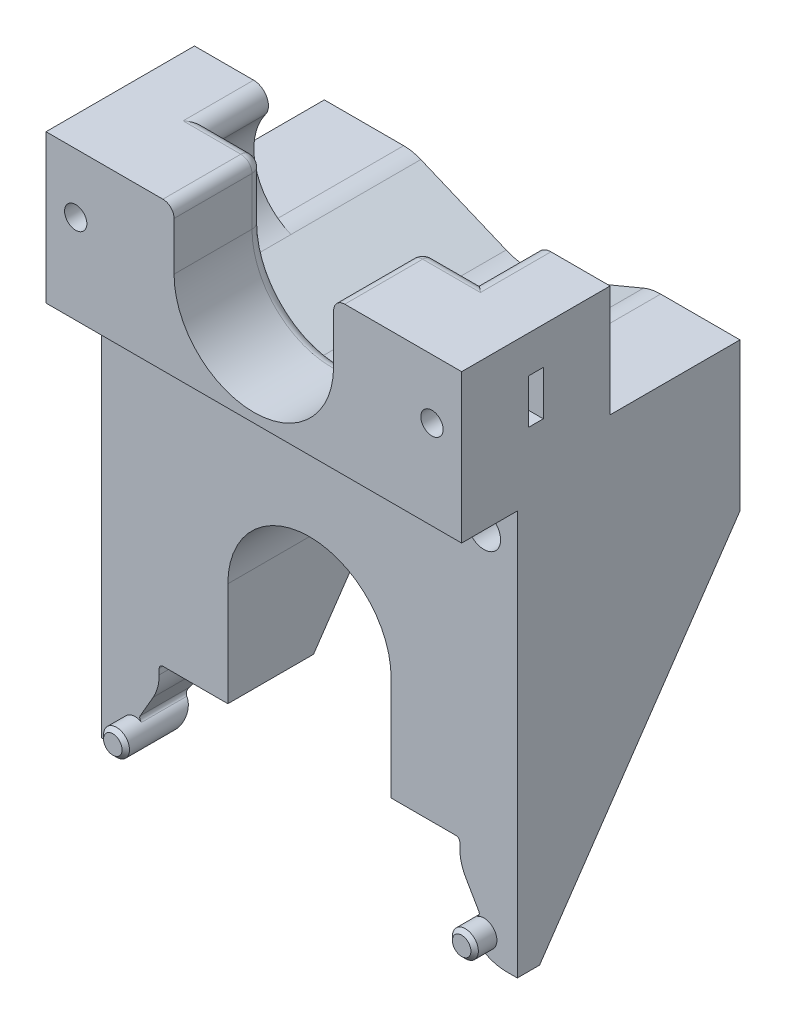
SolidWorks part; units mm, degrees
ref_plane "Front Plane" through (0, 0, 0) normal (0, 0, 1) x (1, 0, 0)
ref_plane "Top Plane" through (0, 0, 0) normal (0, 1, 0) x (1, 0, 0)
ref_plane "Right Plane" through (0, 0, 0) normal (1, 0, 0) x (0, 0, -1)
sketch "Sketch2" plane through (0, 0, 0) normal (0, 0, 1) x (1, 0, 0)
  line L0 (0, 28) -> (0, 0) construction
  line L1 (-23.5, -23.5) -> (23.5, -23.5) construction
  line L2 (-23.5, -23.5) -> (-23.5, 23.5) construction
  line L3 (-23.5, 23.5) -> (23.5, 23.5) construction
  line L4 (23.5, -23.5) -> (23.5, 23.5) construction
  line L5 (-23.5, -23.5) -> (23.5, 23.5) construction
  line L6 (-23.5, 23.5) -> (23.5, -23.5) construction
  line L7 (-28, -37) -> (28, -37) construction
  line L8 (-28, -37) -> (-28, 28) construction
  line L9 (-28, 28) -> (28, 28) construction
  line L10 (28, -37) -> (28, 28) construction
  line L11 (0, 0) -> (-28, 0) construction
  line L12 (-23.5, -25.5) -> (-23.5, -26.5) construction
  line L13 (-23.5, -26.5) -> (23.5, -26.5) construction
  line L14 (23.5, -26.5) -> (23.5, -25.5) construction
  line L15 (-23.5, -25.5) -> (23.5, -25.5) construction
  line L16 (0, 28) -> (0, 29.5) construction
  line L17 (0, 29.5) -> (0, 40) construction
  circle A0 centre (23.5, 23.5) radius 2 construction
  circle A1 centre (-23.5, 23.5) radius 2.25
  circle A2 centre (-23.5, -23.5) radius 1.75
  circle A3 centre (23.5, -23.5) radius 2 construction
  circle A4 centre (23.5, 23.5) radius 2.25
  circle A5 centre (23.5, -23.5) radius 1.75
  circle A6 centre (0, 40) radius 10.5 construction
  point P0 (0, 0)
  point P20 (0, 0)
  point P26 (0, 0)
  point P28 (0, 0)
  point P31 (0, 0)
  dimension "D3" = 4
  dimension "D8" = 21
  dimension "D1" = 47
  dimension "D5" = 56
  dimension "D6" = 65
  dimension "D7" = 1
  dimension "D9" = 1.5
  dimension "D4" = 0.25
sketch "Sketch3" plane through (0, 0, 0) normal (1, 0, 0) x (0, 0, -1)
  line L0 (0, -26.5) -> (0, 0)
  line L1 (0, 0) -> (0, 28)
  line L3 (30, 48) -> (30, 13)
  line L4 (30, 13) -> (3, -26.5)
  line L5 (3, -26.5) -> (0, -26.5)
  line L6 (30, 48) -> (-7.5, 48)
  line L7 (-7.5, 48) -> (-7.5, 28)
  line L8 (-7.5, 28) -> (0, 28)
  line L9 (0, 28) -> (30, 28) construction
  line L10 (3, -26.5) -> (22.1727, -26.5) construction
  dimension "D1" = 15
  dimension "D2" = 20
  dimension "D3" = 30
  dimension "D4" = 3
  dimension "D5" = 55.646
  dimension "D6" = 7.5
extrude "Boss-Extrude1" add sketch "Sketch3" along normal up to vertex (28 mm away) and the other way up to vertex (28 mm away) up to point (28, 28, 0) other way up to point (-28, 28, 0)
sketch "Sketch4" plane through (0, 0, 0) normal (0, 0, 1) x (1, 0, 0)
  line L0 (-28, -26.5) -> (-26.5178, -26.5) construction
  line L1 (-23.5, -26.5) -> (23.5, -26.5) construction
  line L2 (28, -26.5) -> (-28, -26.5) construction
  line L3 (-22.808, -21.3014) -> (-21.0562, -18.2673)
  line L4 (-26.5178, -26.5) -> (26.5178, -26.5)
  line L5 (0, 28) -> (0, -26.5) construction
  line L6 (-23.5, -23.5) -> (-23.5, 23.5) construction
  line L7 (-23.5, -23.5) -> (-22.625, -21.9845) construction
  line L8 (-23.5, -23.5) -> (-22.2626, -24.7374) construction
  line L9 (-23.5, -23.5) -> (23.5, 23.5) construction
  line L10 (-21.75, -23.5) -> (-20.25, -23.5) construction
  line L11 (-23.5, -23.5) -> (23.5, -23.5) construction
  line L12 (-20.25, -15.2584) -> (-20.25, -14.5)
  line L13 (-20.25, -15.2584) -> (-20.25, -23.5) construction
  line L14 (-28, 28) -> (28, 28) construction
  line L15 (-19.75, -14) -> (-11, -14)
  line L16 (0, 0) -> (-28, 0) construction
  line L17 (-11, 0) -> (-11, -14)
  line L19 (28, -26.5) -> (26.5178, -26.5) construction
  line L20 (11, 0) -> (11, -14)
  line L21 (19.75, -14) -> (11, -14)
  line L22 (20.25, -15.2584) -> (20.25, -14.5)
  line L23 (22.808, -21.3014) -> (21.0562, -18.2673)
  arc A0 (-22.2626, -24.7374) -> (-22.625, -21.9845) centre (-23.5, -23.5) ccw
  circle A1 centre (-23.5, -23.5) radius 1.75 construction
  arc A2 (-22.2626, -24.7374) -> (-26.5178, -26.5) centre (-26.5178, -20.4822) cw
  arc A3 (-22.625, -21.9845) -> (-22.808, -21.3014) centre (-22.375, -21.5514) cw
  arc A4 (-21.0562, -18.2673) -> (-20.25, -15.2584) centre (-26.2678, -15.2584) ccw
  arc A5 (-11, 0) -> (11, 0) centre (0, 0) cw
  arc A6 (-20.25, -14.5) -> (-19.75, -14) centre (-19.75, -14.5) cw
  arc A7 (20.25, -14.5) -> (19.75, -14) centre (19.75, -14.5) ccw
  arc A8 (21.0562, -18.2673) -> (20.25, -15.2584) centre (26.2678, -15.2584) cw
  arc A9 (22.625, -21.9845) -> (22.808, -21.3014) centre (22.375, -21.5514) ccw
  arc A10 (22.2626, -24.7374) -> (26.5178, -26.5) centre (26.5178, -20.4822) ccw
  arc A11 (22.2626, -24.7374) -> (22.625, -21.9845) centre (23.5, -23.5) cw
  dimension "D1" = 0.5
  dimension "D5" = 22
  dimension "D2" = 30
  dimension "D3" = 1.5
  dimension "D4" = 42
extrude "Cut-Extrude1" cut sketch "Sketch4" against normal up to next
sketch "Sketch5" plane through (0, 0, 0) normal (0, 0, 1) x (1, 0, 0)
  circle A0 centre (23.5, -23.5) radius 1.75 construction
  circle A1 centre (-23.5, -23.5) radius 1.75 construction
  circle A2 centre (23.5, -23.5) radius 1.75
  circle A3 centre (-23.5, -23.5) radius 1.75
extrude "Boss-Extrude2" add sketch "Sketch5" along normal blind 3
chamfer "Chamfer1" distance 0.5 angle 45 2 edges at (25.25, -23.5, 3) (-21.75, -23.5, 3)
sketch "Sketch6" plane through (0, 0, 0) normal (0, 0, 1) x (1, 0, 0)
  circle A0 centre (23.5, 23.5) radius 2.25 construction
  circle A1 centre (-23.5, 23.5) radius 2.25 construction
  circle A2 centre (23.5, 23.5) radius 2.25
  circle A3 centre (-23.5, 23.5) radius 2.25
extrude "Cut-Extrude2" cut sketch "Sketch6" against normal up to next
sketch "Sketch7" plane through (0, 0, -30) normal (0, 0, -1) x (-1, 0, 0)
  circle A0 centre (-23.5, 23.5) radius 3.75
  circle A1 centre (23.5, 23.5) radius 3.5 construction
  circle A2 centre (23.5, 23.5) radius 3.75
  point P7 (0, 0)
  dimension "D2" = 7
  dimension "D1" = 0.25
extrude "Cut-Extrude3" cut sketch "Sketch7" against normal blind 3
sketch "Sketch8" plane through (0, 0, -30) normal (0, 0, -1) x (-1, 0, 0)
  line L4 (-10.5, 40) -> (10.5, 40) construction
  line L5 (-10.75, 40) -> (-10.75, 48)
  line L6 (-28, 48) -> (28, 48) construction
  line L7 (-10.75, 48) -> (10.75, 48)
  line L8 (10.75, 48) -> (10.75, 40)
  arc A0 (-10.5, 40) -> (10.5, 40) centre (0, 40) ccw construction
  circle A1 centre (0, 40) radius 10.5 construction
  arc A2 (-10.75, 40) -> (10.75, 40) centre (0, 40) ccw
  dimension "D1" = 0.25
extrude "Cut-Extrude4" cut sketch "Sketch8" against normal up to next
sketch "Sketch9" plane through (0, 0, -30) normal (0, 0, -1) x (-1, 0, 0)
  line L1 (3.5, 27.7009) -> (15.0026, 32.5)
  line L2 (0, 40) -> (20, 40) construction
  line L3 (0, 40) -> (0, 27) construction
  line L4 (10.75, 48) -> (28, 48) construction
  line L5 (20.0311, 48) -> (-20.0311, 48)
  line L6 (0, 48) -> (0, 40) construction
  line L7 (-3.5, 27.7009) -> (-15.0026, 32.5)
  arc A0 (-3.5, 27.7009) -> (3.5, 27.7009) centre (0, 36.0897) ccw
  arc A1 (18.42, 44.815) -> (15.0026, 32.5) centre (11.8734, 40) cw
  arc A2 (18.42, 44.815) -> (20.0311, 48) centre (20.0311, 46) cw
  arc A3 (-18.42, 44.815) -> (-15.0026, 32.5) centre (-11.8734, 40) ccw
  arc A4 (-18.42, 44.815) -> (-20.0311, 48) centre (-20.0311, 46) ccw
  point P5 (0, 0)
  point P6 (0, 27)
  point P23 (0, 0)
  point P24 (0, 0)
  point P25 (20.7801, 39.2284)
  dimension "D1" = 20
  dimension "D2" = 7.5
  dimension "D5" = 2
  dimension "D3" = 13
  dimension "D4" = 3.5
extrude "Cut-Extrude5" cut sketch "Sketch9" against normal offset from surface (25.5 mm away) 12 up to face at (0, 39.6563, 7.5)
fillet "Fillet1" radius 1.5 7 edges at (-10.75, 44, -4.5) (0, 29.25, -4.5) (-15.3905, 48, -4.5) (-10.75, 48, 1.5) (10.75, 44, -4.5) (10.75, 48, 1.5) (15.3905, 48, -4.5)
sketch "Sketch10" plane through (0, 0, -30) normal (0, 0, -1) x (-1, 0, 0)
  line L0 (3.5, 27.7009) -> (15.0026, 32.5) construction
  line L1 (17.3129, 32.9626) -> (28, 32.9626)
  line L2 (28, 13) -> (28, 48) construction
  line L3 (20.0311, 48) -> (28, 48) construction
  line L4 (20.0311, 48) -> (28, 48)
  line L5 (28, 32.9626) -> (28, 48)
  line L6 (0, 52.0975) -> (0, 21.7333) construction
  line L7 (-17.3129, 32.9626) -> (-28, 32.9626)
  line L8 (-20.0311, 48) -> (-28, 48)
  line L9 (-28, 32.9626) -> (-28, 48)
  arc A0 (17.3129, 32.9626) -> (15.0026, 32.5) centre (17.3129, 26.9626) ccw
  arc A1 (20.0311, 48) -> (18.42, 44.815) centre (20.0311, 46) ccw construction
  arc A2 (15.0026, 32.5) -> (18.42, 44.815) centre (11.8734, 40) ccw construction
  arc A3 (20.0311, 48) -> (18.42, 44.815) centre (20.0311, 46) ccw
  arc A4 (15.0026, 32.5) -> (18.42, 44.815) centre (11.8734, 40) ccw
  arc A5 (-17.3129, 32.9626) -> (-15.0026, 32.5) centre (-17.3129, 26.9626) cw
  arc A6 (-15.0026, 32.5) -> (-18.42, 44.815) centre (-11.8734, 40) cw
  arc A7 (-20.0311, 48) -> (-18.42, 44.815) centre (-20.0311, 46) cw
  point P12 (0, 21.7333)
  dimension "D1" = 6
extrude "Cut-Extrude6" cut sketch "Sketch10" against normal offset from surface (17.5 mm away) 8 up to face at (0, 38.4455, -4.5)
sketch "Sketch11" plane through (0, 0, -12.5) normal (0, 0, -1) x (-1, 0, 0)
  line L0 (20, 40) -> (28, 40) construction
  line L1 (28, 48) -> (28, 32.9626) construction
  line L2 (20, 40) -> (0, 40) construction
  line L3 (0, 35.0058) -> (0, 45.4651) construction
  circle A0 centre (24, 40) radius 1.25 construction
  arc A2 (15.0026, 32.5) -> (18.42, 44.815) centre (11.8734, 40) ccw construction
  circle A3 centre (24, 40) radius 1.5
  circle A4 centre (-24, 40) radius 1.5
  point P10 (24, 40)
  dimension "D1" = 0.25
  dimension "D2" = 2.5
extrude "Cut-Extrude7" cut sketch "Sketch11" against normal up to next
ref_plane "Plane1" through (0, 0, -2.5) normal (0, 0, -1) x (-1, 0, 0)
sketch "Sketch12" plane through (0, 0, -2.5) normal (0, 0, -1) x (-1, 0, 0)
  line L0 (21, 37) -> (28, 37)
  line L1 (21.25, 37.25) -> (26.75, 37.25) construction
  line L2 (21.25, 37.25) -> (21.25, 42.75) construction
  line L3 (21.25, 42.75) -> (26.75, 42.75) construction
  line L4 (26.75, 37.25) -> (26.75, 42.75) construction
  line L5 (21.25, 37.25) -> (26.75, 42.75) construction
  line L6 (21.25, 42.75) -> (26.75, 37.25) construction
  line L7 (21, 37) -> (21, 43)
  line L8 (21, 43) -> (28, 43)
  line L9 (21, 37) -> (26.75, 37) construction
  line L10 (21, 43) -> (26.75, 43) construction
  line L11 (28, 13) -> (28, 32.9626) construction
  line L12 (28, 43) -> (28, 37)
  line L13 (0, 44.7133) -> (0, 38.4938) construction
  line L14 (-28, 43) -> (-28, 37)
  line L15 (-21, 37) -> (-28, 37)
  line L16 (-21, 37) -> (-21, 43)
  line L17 (-21, 43) -> (-28, 43)
  circle A0 centre (24, 40) radius 1.5 construction
  point P0 (24, 40)
  dimension "D1" = 5.5
extrude "Cut-Extrude8" cut sketch "Sketch12" against normal mid plane 2
equation "\"Tolerance\" = 0.25mm"
equation "\"Pocket_Head_M5\"= 8mm"
equation "\"Pocket_Head_M4\" = 7mm"
equation "\"Pocket_Nut_M4\" = 7mm"
equation "\"Pocket_Nut_M5\"= 8mm"
equation "\"Pocket_Nut_M3\"= 5.5mm"
equation "\"Pocket_Head_M3\"= 5.5mm"
equation "\"D2@Sketch2\"=\"Tolerance\""
equation "\"D4@Sketch2\"=\"Tolerance\""
equation "\"D1@Sketch7\"=\"Tolerance\""
equation "\"D2@Sketch7\"=\"Pocket_Head_M4\""
equation "\"D1@Sketch8\"=\"Tolerance\""
equation "\"D1@Sketch11\"=\"Tolerance\""
equation "\"D1@Sketch12\"=\"Pocket_Nut_M3\""
equation "\"D2@Sketch12\"=\"Tolerance\""
equation "\"D1@Cut-Extrude8\"=( 1.5 + ( \"Tolerance\" * 2 ) )"
